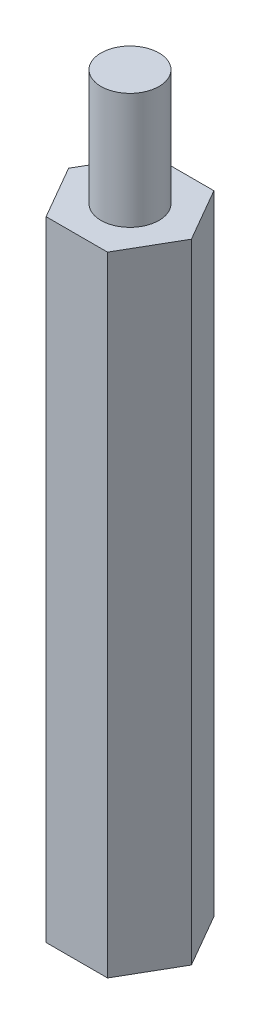
SolidWorks part; units mm, degrees
ref_plane "Front Plane" through (0, 0, 0) normal (0, 0, 1) x (1, 0, 0)
ref_plane "Top Plane" through (0, 0, 0) normal (0, 1, 0) x (1, 0, 0)
ref_plane "Right Plane" through (0, 0, 0) normal (1, 0, 0) x (0, 0, -1)
sketch "Sketch1" plane through (0, 0, 0) normal (0, 1, 0) x (1, 0, 0)
  line L1 (1.5877, -2.75) -> (3.1754, 0)
  line L2 (3.1754, 0) -> (1.5877, 2.75)
  line L3 (1.5877, 2.75) -> (-1.5877, 2.75)
  line L4 (-1.5877, 2.75) -> (-3.1754, 0)
  line L5 (-3.1754, 0) -> (-1.5877, -2.75)
  line L6 (-1.5877, -2.75) -> (1.5877, -2.75)
  circle A0 centre (0, 0) radius 2.75 construction
  dimension "D1" = 5.5
extrude "Boss-Extrude1" add sketch "Sketch1" along normal blind 32.5
sketch "Sketch2" plane through (0, 0, 0) normal (0, -1, 0) x (1, 0, 0)
  circle A0 centre (0, 0) radius 1.5
  dimension "D1" = 3
extrude "Cut-Extrude1" cut sketch "Sketch2" against normal blind 6
extrude "Boss-Extrude2" add sketch "Sketch2<2>" against normal blind 6 from surface starting at face at (0, 32.5, 0)
sketch "Sketch2<2>" plane through (0, 0, 0) normal (0, -1, 0) x (1, 0, 0) same geometry as "Sketch2"
